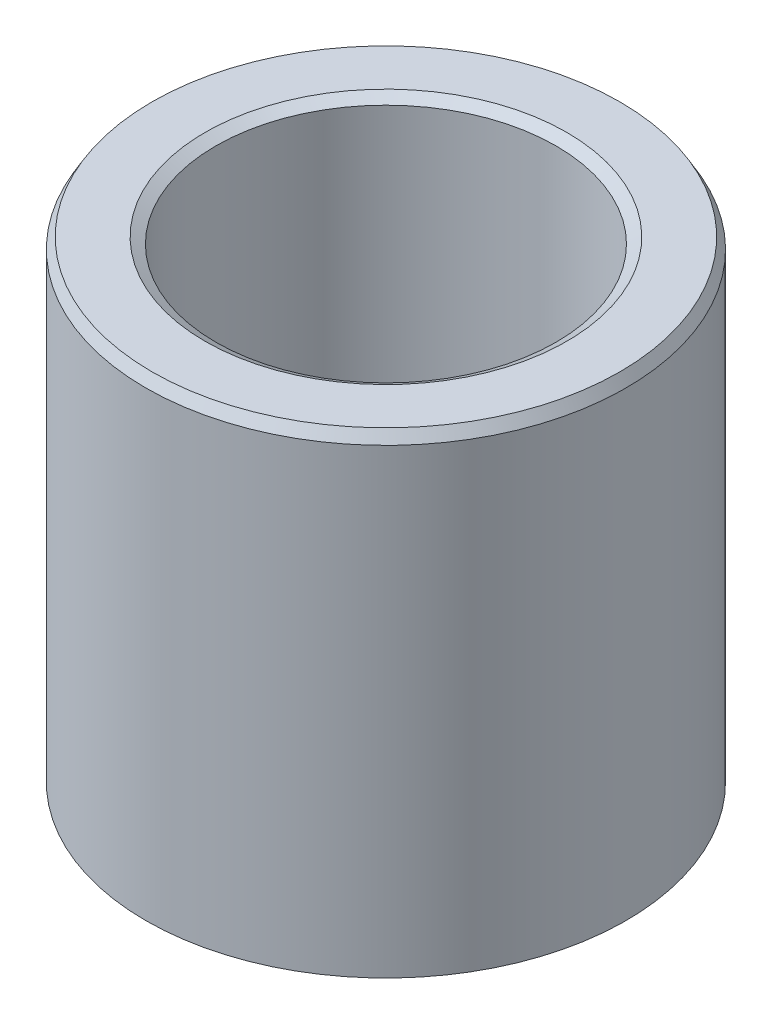
SolidWorks part; units mm, degrees
ref_plane "Front Plane" through (0, 0, 0) normal (0, 0, 1) x (1, 0, 0)
ref_plane "Top Plane" through (0, 0, 0) normal (0, 1, 0) x (1, 0, 0)
ref_plane "Right Plane" through (0, 0, 0) normal (1, 0, 0) x (0, 0, -1)
sketch "Sketch1" plane through (0, 0, 0) normal (0, 1, 0) x (1, 0, 0)
  circle A0 centre (0, 0) radius 27.5
  dimension "SLEEVE_OD" = 55
extrude "Boss-Extrude1" add sketch "Sketch1" along normal blind 54.7818
sketch "Sketch2" plane through (0, 0, 0) normal (0, 1, 0) x (1, 0, 0)
  circle A0 centre (0, 0) radius 19.4787
  dimension "BORE_D" = 38.9575
extrude "Cut-Extrude1" cut sketch "Sketch2" along normal through all
chamfer "Chamfer1" distance 1.2387 angle 30 4 edges at (0, 54.7818, 19.4787) (0, 0, 19.4787) (0, 0, 27.5) (0, 54.7818, 27.5) first distance on face at (0, 54.7818, 19.4787) first distance on face at (0, 0, 19.4787) first distance on face at (0, 54.7818, 27.5)
